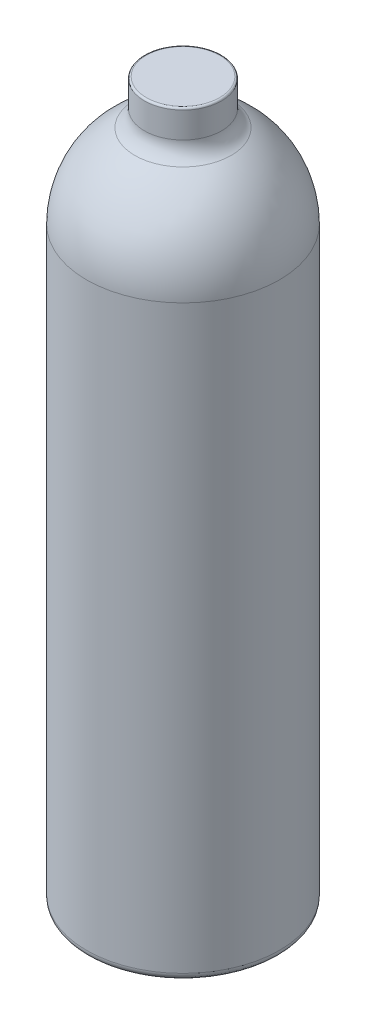
SolidWorks part; units mm, degrees
material "6061 Alloy"
ref_plane "Front Plane" through (0, 0, 0) normal (0, 0, 1) x (1, 0, 0)
ref_plane "Top Plane" through (0, 0, 0) normal (0, 1, 0) x (1, 0, 0)
ref_plane "Right Plane" through (0, 0, 0) normal (1, 0, 0) x (0, 0, -1)
sketch "Sketch2" plane through (0, 0, 0) normal (0, 0, 1) x (1, 0, 0)
  line L6 (202.766, 77.12) -> (519.4206, 74.3566) construction
  line L7 (32.0675, 0) -> (32.0675, 195.58)
  line L10 (0, 238.125) -> (12.827, 238.125)
  line L11 (12.827, 238.125) -> (12.827, 224.9703)
  line L12 (0, 238.125) -> (0, 0.889)
  line L13 (0, 0.889) -> (23.114, 0.889)
  line L14 (23.114, 0.889) -> (23.114, 0)
  line L15 (23.114, 0) -> (32.0675, 0)
  arc A0 (32.0675, 195.58) -> (12.827, 224.9703) centre (0, 195.58) ccw
  dimension "D1" = 238.125
  dimension "D2" = 42.545
  dimension "D3" = 12.827
  dimension "D4" = 23.114
  dimension "D5" = 0.889
  dimension "D6" = 32.0675
revolve "Revolve1" add sketch "Sketch2" angle 360 about L12
fillet "Fillet1" radius 2.54 2 edges at (-23.114, 0.889, 0) (-32.0675, 0, 0)
fillet "Fillet2" radius 0.635 1 edges at (-12.827, 238.125, 0)
fillet "Fillet3" radius 6.35 1 edges at (-12.827, 224.9703, 0)
